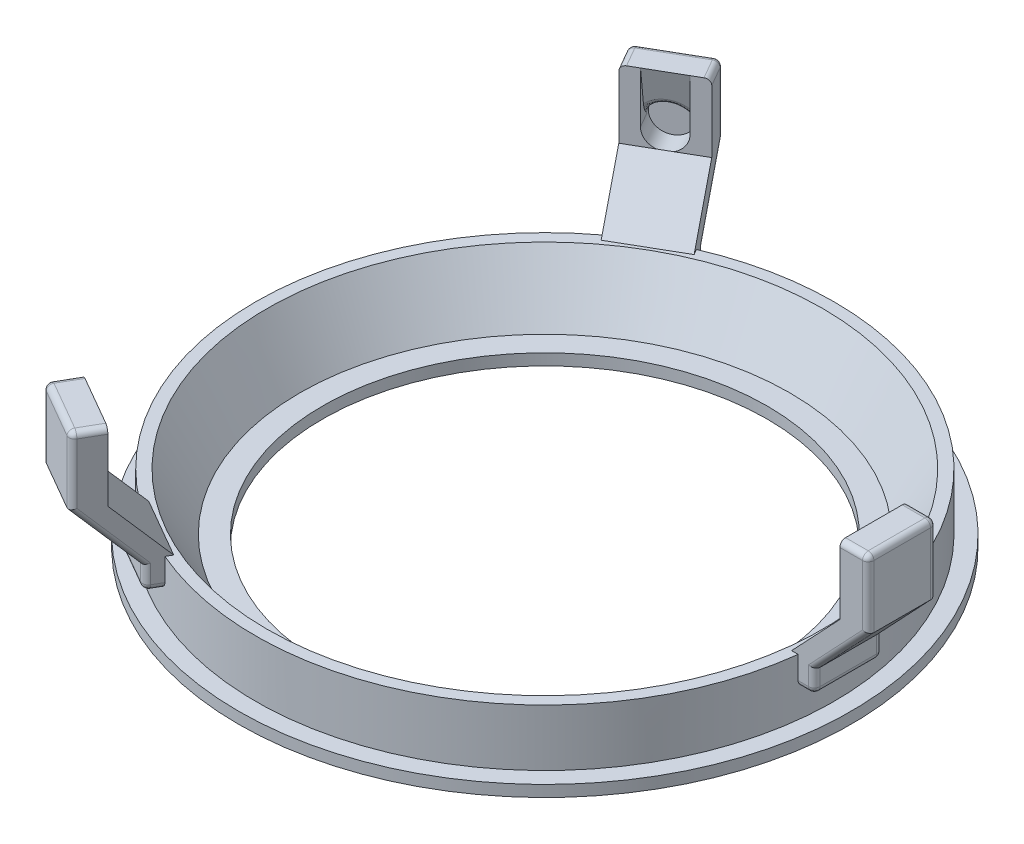
SolidWorks part; units mm, degrees
ref_plane "Front Plane" through (0, 0, 0) normal (0, 0, 1) x (1, 0, 0)
ref_plane "Top Plane" through (0, 0, 0) normal (0, 1, 0) x (1, 0, 0)
ref_plane "Right Plane" through (0, 0, 0) normal (1, 0, 0) x (0, 0, -1)
sketch "Sketch2" plane through (0, 0, 0) normal (0, 0, 1) x (1, 0, 0)
  line L3 (-24.4868, 6) -> (-21.6, 1)
  line L5 (-25.5, 6) -> (-24.4868, 6)
  line L6 (0, 0) -> (0, 5) construction
  line L7 (-25.5, 6) -> (-25.5, 1)
  line L8 (-25.5, 1) -> (-27, 1)
  line L9 (-27, 1) -> (-27, 0)
  line L15 (-21.6, 1) -> (-19.6, 1)
  line L16 (-19.6, 1) -> (-19.6, 0)
  line L17 (-19.6, 0) -> (-27, 0)
  point P0 (-26.812, 0)
  dimension "D1" = 1
  dimension "D2" = 21.6
  dimension "D3" = 27
  dimension "D4" = 1.5
  dimension "D5" = 5
  dimension "D6" = 120
  dimension "D8" = 2
revolve "Revolve1" add sketch "Sketch2" angle 360 about L6
sketch "Sketch3" plane through (0, 0, 0) normal (0, 0, 1) x (1, 0, 0)
  line L5 (27, 1) -> (-27, 1) construction
  line L10 (29, 12) -> (29, 16.5)
  line L11 (29, 16.5) -> (31.5, 16.5)
  line L12 (31.5, 16.5) -> (31.5, 10.5)
  line L13 (24.75, 6) -> (24.75, 1) construction
  line L14 (25.5, 6) -> (-25.5, 6) construction
  line L15 (25.5, 1) -> (-25.5, 1) construction
  line L16 (31.5, 10.5) -> (26.75, 5.4706)
  line L17 (29, 12) -> (29, 10.5)
  line L18 (26.75, 5.4706) -> (26.75, 3.5)
  line L19 (26.75, 3.5) -> (24.75, 3.5)
  line L20 (29, 10.5) -> (24.75, 6)
  line L21 (24.75, 6) -> (24.75, 3.5)
  point P8 (29, 12)
  dimension "D1" = 29
  dimension "D2" = 11
  dimension "D3" = 2.5
  dimension "D4" = 2.5
  dimension "D5" = 2
  dimension "D6" = 24.75
  dimension "D7" = 1.5
  dimension "D8" = 4.5
extrude "Boss-Extrude1" add sketch "Sketch3" along normal blind 3 and the other way blind 3
sketch "Sketch4" plane through (29, 0, 0) normal (-1, 0, 0) x (0, 0, 1)
  line L0 (25.5, 1) -> (-25.5, 1) construction
  circle A0 centre (0, 12) radius 1.6
  dimension "D2" = 3.2
  dimension "D1" = 11
extrude "Cut-Extrude1" cut sketch "Sketch4" against normal blind 1.9
sketch "Sketch5" plane through (0, 0, 3) normal (0, 0, 1) x (1, 0, 0)
  line L0 (29, 16.5) -> (30, 12)
  line L1 (30, 12) -> (29, 12)
  line L2 (29, 16.5) -> (29, 10.5) construction
  line L3 (29, 16.5) -> (29, 12)
  dimension "D1" = 4.5
  dimension "D2" = 1
extrude "Cut-Extrude2" cut sketch "Sketch5" against normal blind 3.2 from offset 1.4 offset against normal yes
fillet "Fillet1" radius 0.5 1 edges at (29.6444, 13.6, 0)
fillet "Fillet2" radius 0.5 9 edges at (26.0365, 3.5, -3) (26.75, 4.4853, -3) (29.125, 7.9853, -3) (31.5, 13.5, -3) (31.5, 16.5, 0) (31.5, 13.5, 3) (29.125, 7.9853, 3) (26.75, 4.4853, 3) (26.0365, 3.5, 3)
fillet "Fillet3" radius 0.5 3 edges at (26.6036, 3.6464, -2.8536) (26.6036, 3.6464, 2.8536) (26.75, 3.5, 0)
fillet "Fillet4" radius 0.5 4 edges at (31.3536, 16.3536, 2.8536) (31.3536, 16.3536, -2.8536) (30, 16.5, 3) (30, 16.5, -3)
pattern_circular "CirPattern1" count 3 over 360 about axis through (0, 6, 0) along (0, -1, 0) of "Boss-Extrude1", "Cut-Extrude1", "Cut-Extrude2", "Fillet1", "Fillet2", "Fillet3", "Fillet4"
